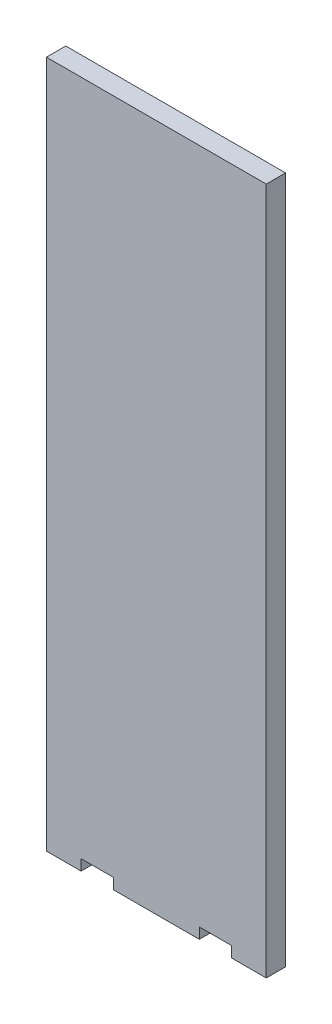
SolidWorks part; units mm, degrees
ref_plane "Front Plane" through (0, 0, 0) normal (0, 0, 1) x (1, 0, 0)
ref_plane "Top Plane" through (0, 0, 0) normal (0, 1, 0) x (1, 0, 0)
ref_plane "Right Plane" through (0, 0, 0) normal (1, 0, 0) x (0, 0, -1)
sketch "Sketch1" plane through (0, 0, 0) normal (0, 0, 1) x (1, 0, 0)
  line L0 (212, -36.5) -> (-18, -36.5) construction
  line L1 (-5.3, -36.5) -> (199.3, -36.5)
  line L2 (-5.3, -36.5) -> (-5.3, 603.5)
  line L3 (-5.3, 603.5) -> (199.3, 603.5)
  line L4 (199.3, -36.5) -> (199.3, 603.5)
  dimension "D1" = 640
extrude "Boss-Extrude1" add sketch "Sketch1" along normal blind 18
hole_wizard "Ø3.0 (3) Diameter Hole1" positions "Sketch2" profile "Sketch3" hole size "Ø3.0" standard "ISO"
sketch "Sketch2" plane through (0, 0, 0) normal (0, 0, -1) x (-1, 0, 0)
  line L0 (-20.2, 476.25) -> (-20.2, 478.5) construction
  line L1 (-21.45, 476.25) -> (-18.95, 476.25) construction
  line L2 (-20.2, 478.5) -> (-23.7, 478.5) construction
  line L3 (-173.8, 476.25) -> (-173.8, 480.75) construction
  line L4 (-172.55, 476.25) -> (-175.05, 476.25) construction
  line L5 (-175.05, 480.75) -> (-172.55, 480.75) construction
  line L7 (-173.8, 192.75) -> (-173.8, 188.25) construction
  line L8 (-175.05, 192.75) -> (-172.55, 192.75) construction
  line L10 (-172.55, 188.25) -> (-175.05, 188.25) construction
  line L11 (-20.2, -3.75) -> (-20.2, 0.75) construction
  line L12 (-21.45, -3.75) -> (-18.95, -3.75) construction
  line L13 (-18.95, 0.75) -> (-21.45, 0.75) construction
  line L14 (-173.8, -3.75) -> (-173.8, 0.75) construction
  line L15 (-172.55, -3.75) -> (-175.05, -3.75) construction
  line L16 (-175.05, 0.75) -> (-172.55, 0.75) construction
  point P2 (-20.2, 478.5)
  point P13 (-173.8, 478.5)
  point P37 (-173.8, 190.5)
  point P39 (-20.2, 190.5)
  point P50 (-20.2, -1.5)
  point P60 (-173.8, -1.5)
  point P61 (-131.9476, 597.7732)
  point P64 (-61.0278, 597.7732)
  point P67 (-131.9476, -30.5832)
  point P69 (-61.0278, -30.5832)
sketch "Sketch3" plane through (61.0278, -30.5832, 0) normal (1, 0, 0) x (0, 1, 0)
  line L0 (0, 0) -> (0, 5.9013)
  line L1 (0, 5.9013) -> (1.5, 5)
  line L2 (1.5, 5) -> (1.5, 0)
  line L5 (1.5, 0) -> (0, 0)
  line L10 (0, 5.9013) -> (-1.5, 5) construction
  line L11 (0, -6.35) -> (0, 107.95) construction
  dimension "Hole Dia." = 3
  dimension "Hole Depth" = 5
  dimension "Drill Angle" = 118
sketch "Sketch4" plane through (0, 0, 0) normal (0, 0, -1) x (-1, 0, 0)
  line L1 (-27, -36.5) -> (-57, -36.5)
  line L2 (-27, -36.5) -> (-27, -26.5)
  line L3 (-27, -26.5) -> (-57, -26.5)
  line L4 (-57, -36.5) -> (-57, -26.5)
  line L6 (5.3, -15.2275) -> (-199.3, -15.2275) construction
  line L15 (5.3, 603.5) -> (5.3, -36.5) construction
  line L16 (-199.3, -36.5) -> (-199.3, 603.5) construction
  line L17 (-137, -36.5) -> (-137, -26.5)
  line L18 (-97, -15.2275) -> (-97, -26.5) construction
  line L19 (-167, -26.5) -> (-137, -26.5)
  line L20 (-167, -36.5) -> (-167, -26.5)
  line L21 (-167, -36.5) -> (-137, -36.5)
  point P6 (0, 0)
  point P14 (-97, -12.7784)
  point P17 (0, 0)
  point P22 (0, 0)
  dimension "D1" = 30
  dimension "D2" = 40
extrude "Cut-Extrude1" cut sketch "Sketch4" against normal blind 18
